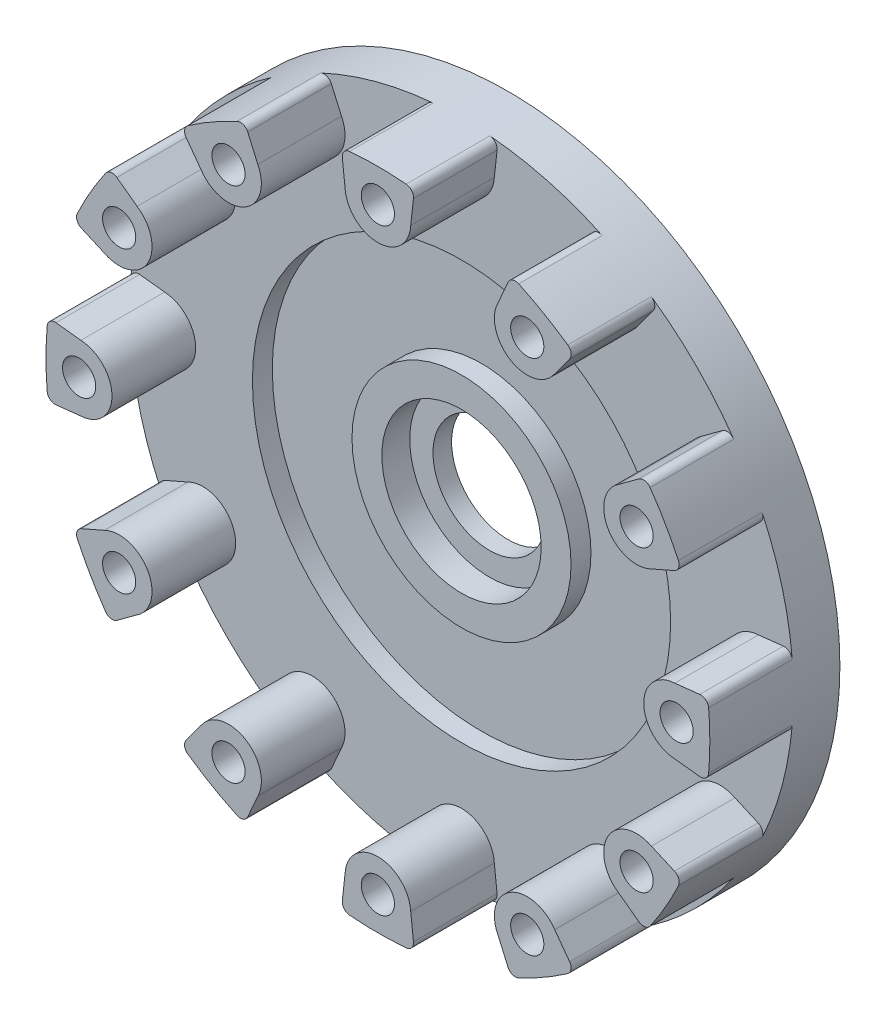
SolidWorks part; units mm, degrees
ref_plane "Front Plane" through (0, 0, 0) normal (0, 0, 1) x (1, 0, 0)
ref_plane "Top Plane" through (0, 0, 0) normal (0, 1, 0) x (1, 0, 0)
ref_plane "Right Plane" through (0, 0, 0) normal (1, 0, 0) x (0, 0, -1)
sketch "Sketch1" plane through (0, 0, 0) normal (0, 0, 1) x (1, 0, 0)
  circle A0 centre (0, 0) radius 50
  dimension "D1" = 100
extrude "Boss-Extrude1" add sketch "Sketch1" against normal blind 7
sketch "Sketch2" plane through (0, 0, 0) normal (0, 0, 1) x (1, 0, 0)
  line L0 (0, 0) -> (44.7277, 4.9425) construction
  line L1 (44.7277, 4.9425) -> (48.4901, 5.3583)
  line L2 (0, 0) -> (44.7277, -4.9425) construction
  line L3 (44.7277, -4.9425) -> (48.4901, -5.3583)
  circle A0 centre (0, 0) radius 45 construction
  arc A1 (44.7277, 4.9425) -> (44.7277, -4.9425) centre (45, 0) ccw
  arc A2 (44.7277, -4.9425) -> (44.7277, 4.9425) centre (0, 0) ccw construction
  circle A3 centre (0, 0) radius 50 construction
  arc A4 (49.8175, 4.2679) -> (49.8175, -4.2679) centre (0, 0) cw
  arc A5 (48.4901, -5.3583) -> (49.8175, -4.2679) centre (48.6219, -4.1655) ccw
  arc A6 (48.4901, 5.3583) -> (49.8175, 4.2679) centre (48.6219, 4.1655) cw
  circle A7 centre (45, 0) radius 2.5
  point P13 (49.6975, -5.4917)
  point P16 (49.6975, 5.4917)
  dimension "D1" = 90
  dimension "D2" = 4.95
  dimension "D3" = 1.2
  dimension "D4" = 5
extrude "Boss-Extrude2" add sketch "Sketch2" along normal blind 12.6
pattern_circular "CirPattern1" count 12 over 360 about axis through (0, 0, -7) along (0, 0, 1) of "Boss-Extrude2" reverse direction yes
sketch "Sketch3" plane through (0, 0, 0) normal (0, 0, 1) x (1, 0, 0)
  circle A0 centre (0, 0) radius 12
  dimension "D1" = 24
extrude "Cut-Extrude1" cut sketch "Sketch3" against normal through all
sketch "Sketch4" plane through (0, 0, 0) normal (0, 0, 1) x (1, 0, 0)
  line L0 (-16.5, 0) -> (-31.5, 0) construction
  circle A0 centre (0, 0) radius 24 construction
  circle A1 centre (0, 0) radius 31.5
  circle A2 centre (0, 0) radius 16.5
  point P7 (-24, 0)
  point P8 (-24, 0)
  dimension "D1" = 48
  dimension "D2" = 15
extrude "Cut-Extrude2" cut sketch "Sketch4" against normal blind 3
sketch "Sketch5" plane through (0, 0, 0) normal (0, 0, 1) x (1, 0, 0)
  circle A0 centre (0, 0) radius 12
  circle A1 centre (0, 0) radius 8.5
  circle A2 centre (0, 0) radius 12 construction
  dimension "D1" = 17
extrude "Boss-Extrude3" add sketch "Sketch5" against normal up to surface (2.8 mm away) from offset 4.2 up to face at (12, 0, -7) offset against normal yes
scale "Scale1" scale about centroid uniform scaling yes scale factor 0.4
